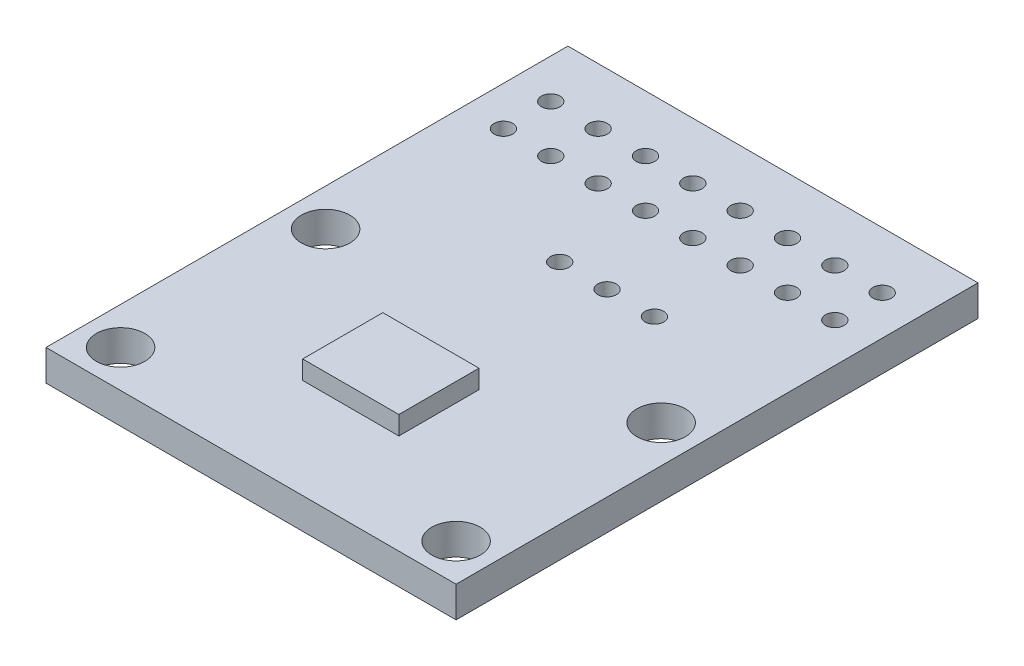
SolidWorks part; units mm, degrees
ref_plane "Front Plane" through (0, 0, 0) normal (0, 0, 1) x (1, 0, 0)
ref_plane "Top Plane" through (0, 0, 0) normal (0, 1, 0) x (1, 0, 0)
ref_plane "Right Plane" through (0, 0, 0) normal (1, 0, 0) x (0, 0, -1)
ref_plane "Plane1" through (0, 0.83, 0) normal (0, 1, 0) x (1, 0, 0)
sketch "Sketch1" plane through (0, 0.83, 0) normal (0, 1, 0) x (1, 0, 0)
  line L0 (11, -14) -> (11, 14)
  line L1 (11, 14) -> (-11, 14)
  line L2 (-11, 14) -> (-11, -14)
  line L3 (-11, -14) -> (11, -14)
extrude "Boss-Extrude1" add sketch "Sketch1" against normal blind 1.66
sketch "Sketch2" plane through (0, 0.83, 0) normal (0, 1, 0) x (-1, 0, 0)
  line L0 (-2.58, 8.65) -> (2.58, 8.65)
  line L1 (2.58, 8.65) -> (2.58, 4.35)
  line L2 (2.58, 4.35) -> (-2.58, 4.35)
  line L3 (-2.58, 4.35) -> (-2.58, 8.65)
extrude "Boss-Extrude2" add sketch "Sketch2" along normal blind 1
hole_wizard "Ø2.6 (2.6) Diameter Hole1" positions "Sketch4" profile "Sketch3" hole size "Ø2.6" standard "ANSI Metric"
sketch "Sketch4" plane through (0, -0.83, 0) normal (0, -1, 0) x (-1, 0, 0)
  point P0 (9, -1)
  point P1 (-9, -1)
  point P2 (9, -12)
  point P3 (-9, -12)
sketch "Sketch3" plane through (-9, -0.83, 1) normal (1, 0, 0) x (0, 0, -1)
  line L0 (0, 0) -> (0, 2.66)
  line L1 (0, 2.66) -> (1.3, 2.66)
  line L2 (1.3, 2.66) -> (1.3, 0)
  line L5 (1.3, 0) -> (0, 0)
  line L11 (0, -6.35) -> (0, 107.95) construction
  dimension "Thru Hole Dia." = 2.6
  dimension "Thru Hole Depth" = 2.66
ref_plane "Plane2" through (0, 0, 6.5) normal (0, 0, -1) x (-1, 0, 0)
ref_axis "Axis1" through (0, -0.963, 6.5) along (0, 1, 0)
sketch "Sketch5" plane through (0, 0.83, 0) normal (0, 1, 0) x (1, 0, 0)
  line L0 (34.6032, 177.1459) -> (301.2699, 177.1459) construction
  line L2 (-2.5, 5) -> (5.2, 5)
  line L3 (-2.5, 5) -> (-2.5, 2.5)
  line L4 (11, -14) -> (11, 14)
  line L5 (11, 14) -> (-11, 14)
  line L6 (-11, 14) -> (-11, -14)
  line L7 (-11, -14) -> (11, -14)
  line L8 (11, -14) -> (11, 14)
  line L9 (11, 14) -> (-11, 14)
  line L10 (-11, 14) -> (-11, -14)
  line L11 (-11, -14) -> (11, -14)
  line L12 (-2.58, -8.65) -> (2.58, -8.65)
  line L13 (-2.58, -4.35) -> (-2.58, -8.65)
  line L14 (2.58, -4.35) -> (-2.58, -4.35)
  line L15 (2.58, -8.65) -> (2.58, -4.35)
  line L16 (-2.58, -8.65) -> (2.58, -8.65)
  line L17 (-2.58, -4.35) -> (-2.58, -8.65)
  line L18 (2.58, -4.35) -> (-2.58, -4.35)
  line L19 (2.58, -8.65) -> (2.58, -4.35)
  line L20 (-2.5, 2.5) -> (5.2, 2.5)
  line L21 (5.2, 5) -> (5.2, 2.5)
  line L22 (-10, 12.2) -> (10, 12.2)
  line L23 (-10, 12.2) -> (-10, 7.2)
  line L24 (-10, 7.2) -> (10, 7.2)
  line L25 (10, 12.2) -> (10, 7.2)
  point P18 (0, 12.2)
  dimension "D3" = 11.5
  dimension "D4" = 1.8
  dimension "D5" = 2.5
  dimension "D6" = 5
  dimension "D7" = 20
  dimension "D8" = 7.7
  dimension "D9" = 8.5
  dimension "D1" = 0
  dimension "D2" = 0
sketch "Sketch6" plane through (0, 0.83, 0) normal (0, 1, 0) x (1, 0, 0)
  line L0 (-8.89, 10.97) -> (-8.89, 8.43) construction
  line L1 (8.89, 10.97) -> (8.89, 8.43) construction
  line L2 (-8.89, 9.7) -> (8.89, 9.7) construction
  line L3 (0, 12.2) -> (0, 7.2) construction
  line L4 (-2.58, -8.65) -> (2.58, -8.65)
  line L5 (2.58, -8.65) -> (2.58, -4.35)
  line L6 (2.58, -4.35) -> (-2.58, -4.35)
  line L7 (-2.58, -4.35) -> (-2.58, -8.65)
  line L8 (-2.58, -8.65) -> (2.58, -8.65) construction
  line L9 (2.58, -8.65) -> (2.58, -4.35) construction
  line L10 (2.58, -4.35) -> (-2.58, -4.35) construction
  line L11 (-2.58, -4.35) -> (-2.58, -8.65) construction
  line L12 (11, -14) -> (11, 14)
  line L13 (11, 14) -> (-11, 14)
  line L14 (-11, 14) -> (-11, -14)
  line L15 (-11, -14) -> (11, -14)
  line L16 (11, -14) -> (11, 14) construction
  line L17 (11, 14) -> (-11, 14) construction
  line L18 (-11, 14) -> (-11, -14) construction
  line L19 (-11, -14) -> (11, -14) construction
  line L20 (5.2, 5) -> (-2.5, 5)
  line L21 (5.2, 2.5) -> (5.2, 5)
  line L22 (-2.5, 2.5) -> (5.2, 2.5)
  line L23 (-2.5, 5) -> (-2.5, 2.5)
  line L24 (5.2, 5) -> (-2.5, 5) construction
  line L25 (5.2, 2.5) -> (5.2, 5) construction
  line L26 (-2.5, 2.5) -> (5.2, 2.5) construction
  line L27 (-2.5, 5) -> (-2.5, 2.5) construction
  line L28 (10, 12.2) -> (-10, 12.2)
  line L29 (-10, 12.2) -> (-10, 7.2)
  line L30 (-10, 7.2) -> (10, 7.2)
  line L31 (10, 7.2) -> (10, 12.2)
  line L32 (10, 12.2) -> (-10, 12.2) construction
  line L33 (-10, 12.2) -> (-10, 7.2) construction
  line L34 (-10, 7.2) -> (10, 7.2) construction
  line L35 (10, 7.2) -> (10, 12.2) construction
  circle A0 centre (-8.89, 10.97) radius 0.5
  circle A1 centre (-8.89, 8.43) radius 0.5
  circle A2 centre (-6.35, 10.97) radius 0.5
  circle A3 centre (-6.35, 8.43) radius 0.5
  circle A4 centre (-3.81, 10.97) radius 0.5
  circle A5 centre (-3.81, 8.43) radius 0.5
  circle A6 centre (-1.27, 10.97) radius 0.5
  circle A7 centre (-1.27, 8.43) radius 0.5
  circle A8 centre (1.27, 10.97) radius 0.5
  circle A9 centre (1.27, 8.43) radius 0.5
  circle A10 centre (3.81, 10.97) radius 0.5
  circle A11 centre (3.81, 8.43) radius 0.5
  circle A12 centre (6.35, 10.97) radius 0.5
  circle A13 centre (6.35, 8.43) radius 0.5
  circle A14 centre (8.89, 10.97) radius 0.5
  circle A15 centre (8.89, 8.43) radius 0.5
  circle A16 centre (-1.19, 3.75) radius 0.5
  circle A17 centre (1.35, 3.75) radius 0.5
  circle A18 centre (3.89, 3.75) radius 0.5
  point P52 (0, 9.7)
  point P53 (0, 9.7)
  point P65 (1.35, 5)
  point P67 (5.2, 3.75)
  dimension "D5" = 1
  dimension "D6" = 2.54
  dimension "D1" = 0
  dimension "D2" = 0
  dimension "D3" = 0
  dimension "D4" = 0
  dimension "D7" = 8
  dimension "D8" = 3
extrude "Cut-Extrude1" cut sketch "Sketch6" against normal through all
